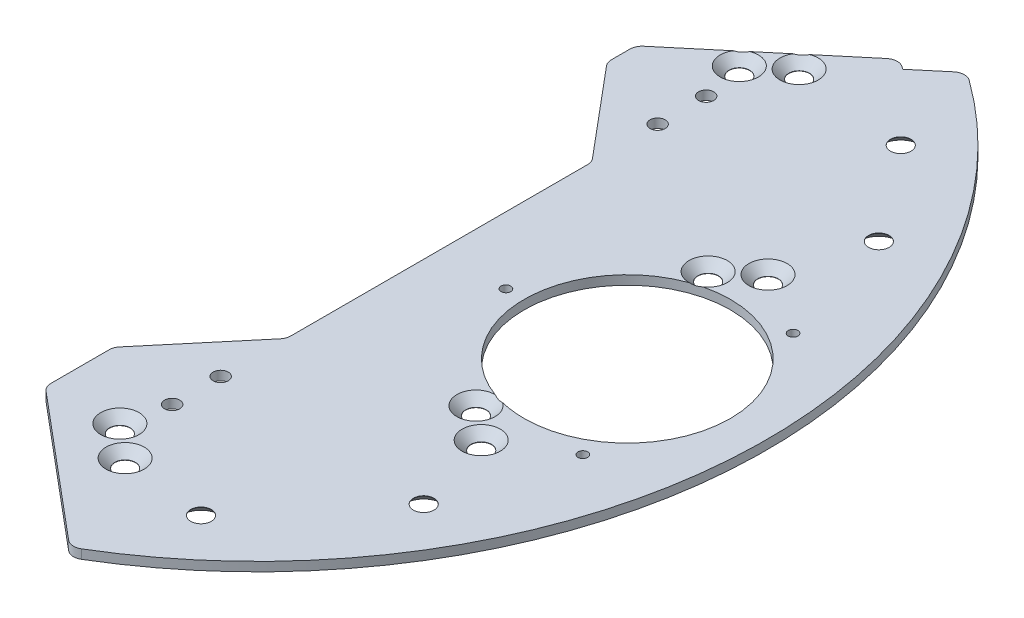
SolidWorks part; units mm, degrees
ref_plane "Plano frontal" through (0, 0, 0) normal (0, 0, 1) x (1, 0, 0)
ref_plane "Plano superior" through (0, 0, 0) normal (0, 1, 0) x (1, 0, 0)
ref_plane "Plano direito" through (0, 0, 0) normal (1, 0, 0) x (0, 0, -1)
sketch "Esboço1" plane through (0, 0, 0) normal (0, 1, 0) x (1, 0, 0)
  line L2 (0, 0) -> (17, 0) construction
  line L3 (17, -85.3229) -> (17, 85.3229)
  arc A0 (17, -85.3229) -> (17, 85.3229) centre (0, 0) ccw
  point P9 (17, 0)
  dimension "D1" = 174
  dimension "D2" = 17
extrude "Ressalto-extrusão1" add sketch "Esboço1" along normal blind 1.5 contours L3 A0
sketch "Esboço2" plane through (0, 1.5, 0) normal (0, 1, 0) x (1, 0, 0)
  line L0 (0, 0) -> (61, 0) construction
  line L1 (61, 0) -> (41, 0) construction
  line L2 (61, 0) -> (71, 17.3205) construction
  line L3 (61, 0) -> (71, -17.3205) construction
  circle A0 centre (61, 0) radius 17
  point P6 (41, 0)
  dimension "D2" = 34
  dimension "D1" = 61
  dimension "D3" = 20
  dimension "D4" = 3
extrude "Corte-extrusão1" cut sketch "Esboço2" against normal through all
hole_wizard "Furo roscado de M21" positions "3DSketch1" profile "Esboço3" tap size "M2" standard "ISO" end condition up to next
sketch3d "3DSketch1"
  point P0 (71, 1.5, 17.3205)
  point P3 (41, 1.5, 0)
  point P6 (71, 1.5, -17.3205)
sketch "Esboço3" plane through (71, 1.5, 17.3205) normal (1, 0, 0) x (0, 0, 1)
  line L0 (0, 0) -> (0, 1.5)
  line L1 (0, 1.5) -> (0.8, 1.5)
  line L2 (0.8, 1.5) -> (0.8, 0)
  line L5 (0.8, 0) -> (0, 0)
  line L11 (0, -6.35) -> (0, 107.95) construction
  dimension "Thru Tap Drill Dia." = 1.6
  dimension "Thru Tap Drill Depth" = 1.5
cosmetic thread "Rosca de furo1" parameters "D2"=2
cosmetic thread "Rosca de furo2" parameters "D2"=2
cosmetic thread "Rosca de furo3" parameters "D2"=2
sketch "Esboço4" plane through (0, 1.5, 0) normal (0, 1, 0) x (1, 0, 0)
  line L0 (0, 0) -> (66.6459, 55.9225) construction
  line L1 (0, 0) -> (61, 0) construction
  line L2 (0, 0) -> (66.6459, -55.9225) construction
  line L3 (50.8976, 74.6906) -> (82.3942, 37.1544) construction
  line L4 (82.3942, 37.1544) -> (70.8874, 27.4991) construction
  line L5 (70.8874, 27.4991) -> (55.1391, 46.2672) construction
  line L6 (55.1391, 46.2672) -> (39.3908, 65.0353) construction
  line L7 (39.3908, 65.0353) -> (50.8976, 74.6906) construction
  line L8 (48.2004, 72.4274) -> (79.697, 34.8912) construction
  line L9 (50.8976, -74.6906) -> (82.3942, -37.1544) construction
  line L10 (82.3942, -37.1544) -> (70.8874, -27.4991) construction
  line L11 (70.8874, -27.4991) -> (39.3908, -65.0353) construction
  line L12 (39.3908, -65.0353) -> (50.8976, -74.6906) construction
  line L13 (63.9487, -53.6593) -> (79.697, -34.8912) construction
  line L14 (63.9487, -53.6593) -> (48.2004, -72.4274) construction
  line L15 (17, -85.3229) -> (17, 85.3229) construction
  line L16 (30, 0) -> (30, 24.445)
  line L17 (29.5321, 25.7306) -> (17, 40.6658)
  line L18 (30, 0) -> (30, -24.445)
  line L19 (29.5321, -25.7306) -> (17, -40.6658)
  line L20 (17, 40.6658) -> (17, -40.6658)
  arc A0 (17, -85.3229) -> (17, 85.3229) centre (0, 0) ccw construction
  arc A1 (30, 24.445) -> (29.5321, 25.7306) centre (28, 24.445) ccw
  arc A2 (30, -24.445) -> (29.5321, -25.7306) centre (28, -24.445) cw
  point P17 (66.6459, -55.9225)
  point P21 (66.6459, 55.9225)
  point P24 (17, 0)
  point P26 (30, 0)
  point P36 (30, 25.173)
  point P39 (30, -25.173)
  dimension "D8" = 2
  dimension "D1" = 40
  dimension "D2" = 40
  dimension "D3" = 49
  dimension "D4" = 11.5
  dimension "D5" = 49
  dimension "D6" = 11.5
  dimension "D7" = 30
extrude "Corte-extrusão2" cut sketch "Esboço4" against normal blind 2.5
sketch "Esboço5" plane through (0, 1.5, 0) normal (0, 1, 0) x (1, 0, 0)
  line L0 (41.7531, 62.2201) -> (68.5252, 30.3144) construction
  line L2 (70.8874, 27.4991) -> (55.1391, 46.2672) construction
  line L3 (41.7531, 62.2201) -> (28.4239, 51.0356) construction
  line L4 (68.5252, 30.3144) -> (55.196, 19.1299) construction
  line L5 (0, 0) -> (66.6459, -55.9225) construction
  line L6 (70.8874, -27.4991) -> (39.3908, -65.0353) construction
  line L7 (41.7531, -62.2201) -> (68.5252, -30.3144) construction
  line L8 (41.7531, -62.2201) -> (28.4239, -51.0356) construction
  line L9 (68.5252, -30.3144) -> (55.196, -19.1299) construction
  point P0 (33.7862, 55.5351)
  point P4 (55.1391, 46.2672)
  point P10 (60.5583, 23.6294)
  point P11 (55.1391, -46.2672)
  point P12 (60.5583, -23.6294)
  point P20 (55.1391, -46.2672)
  point P22 (33.7862, -55.5351)
  dimension "D1" = 41.65
  dimension "D2" = 10.4
  dimension "D3" = 7
  dimension "D4" = 7
  dimension "D5" = 10.4
  dimension "D6" = 41.65
  dimension "D7" = 10.4
  dimension "D8" = 7
  dimension "D9" = 7
  dimension "D10" = 10.4
hole_wizard "Escareado para parafuso com cabeça escareada chata de M32" positions "3DSketch2" profile "Esboço6" countersink size "M3" standard "ISO" end condition up to next
sketch3d "3DSketch2"
  point P0 (33.7862, 1.5, -55.5351)
  point P3 (28.4239, 1.5, -51.0356)
  point P6 (60.5583, 1.5, -23.6294)
  point P9 (55.196, 1.5, -19.1299)
sketch "Esboço6" plane through (33.7862, 1.5, -55.5351) normal (1, 0, 0) x (0, 0, 1)
  line L0 (0, 0) -> (0, 1.5)
  line L1 (0, 1.5) -> (1.7, 1.5)
  line L2 (1.7, 1.5) -> (1.7, 1.45)
  line L3 (1.7, 1.45) -> (3.15, 0)
  line L5 (3.15, 0) -> (0, 0)
  line L6 (-1.7, 1.45) -> (-3.15, 0) construction
  line L11 (0, -6.35) -> (0, 107.95) construction
  dimension "Thru Hole Dia." = 3.4
  dimension "Thru Hole Depth" = 1.5
  dimension "Near C'Sink Dia." = 6.3
  dimension "Near C'Sink Angle" = 90
hole_wizard "Escareado para parafuso com cabeça escareada chata de M33" positions "3DSketch3" profile "Esboço7" countersink size "M3" standard "ISO" end condition up to next
sketch3d "3DSketch3"
  point P0 (55.196, 1.5, 19.1299)
  point P3 (60.5583, 1.5, 23.6294)
  point P6 (28.4239, 1.5, 51.0356)
  point P9 (33.7862, 1.5, 55.5351)
sketch "Esboço7" plane through (55.196, 1.5, 19.1299) normal (1, 0, 0) x (0, 0, 1)
  line L0 (0, 0) -> (0, 1.5)
  line L1 (0, 1.5) -> (1.7, 1.5)
  line L2 (1.7, 1.5) -> (1.7, 1.45)
  line L3 (1.7, 1.45) -> (3.15, 0)
  line L5 (3.15, 0) -> (0, 0)
  line L6 (-1.7, 1.45) -> (-3.15, 0) construction
  line L11 (0, -6.35) -> (0, 107.95) construction
  dimension "Thru Hole Dia." = 3.4
  dimension "Thru Hole Depth" = 1.5
  dimension "Near C'Sink Dia." = 6.3
  dimension "Near C'Sink Angle" = 90
sketch "Esboço8" plane through (0, 1.5, 0) normal (0, 1, 0) x (1, 0, 0)
  line L0 (0, 0) -> (0, 87) construction
  line L1 (27.5, 80) -> (34.1906, 80)
  line L2 (34.1906, 80) -> (34.1906, 87)
  line L3 (34.1906, 87) -> (0, 87)
  line L4 (0, 87) -> (0, 80)
  line L5 (0, 55) -> (27.5, 55)
  line L6 (27.5, 55) -> (27.5, 80)
  line L7 (0, 80) -> (27.5, 80) construction
  line L8 (0, 80) -> (0, 55)
  arc A1 (17, -85.3229) -> (17, 85.3229) centre (0, 0) ccw construction
  point P3 (0, 80)
  point P14 (27.5, 80)
  dimension "D1" = 87
  dimension "D2" = 80
  dimension "D3" = 27.5
  dimension "D4" = 25
sketch "Esboço10" plane through (0, 0, 0) normal (0, -1, 0) x (1, 0, 0)
  line L0 (0, 0) -> (78, 0) construction
  line L1 (0, 0) -> (64.9519, -37.5) construction
  line L2 (0, 0) -> (64.9519, 37.5) construction
  line L3 (0, 0) -> (48.2091, 57.4533) construction
  line L4 (0, 0) -> (53.033, -53.033) construction
  circle A0 centre (61, 0) radius 17 construction
  dimension "D1" = 30
  dimension "D2" = 45
  dimension "D3" = 50
  dimension "D4" = 30
  dimension "D5" = 75
hole_wizard "Escareado para parafuso com cabeça escareada chata de M34" positions "3DSketch4" profile "Esboço11" countersink size "M3" standard "ISO"
sketch3d "3DSketch4"
  point P0 (48.2091, 0, 57.4533)
  point P3 (64.9519, 0, 37.5)
  point P6 (64.9519, 0, -37.5)
  point P9 (53.033, 0, -53.033)
sketch "Esboço11" plane through (48.2091, 0, 57.4533) normal (1, 0, 0) x (0, 0, -1)
  line L0 (0, 0) -> (0, 8.2715)
  line L1 (0, 8.2715) -> (1.7, 7.25)
  line L2 (1.7, 7.25) -> (1.7, 1.45)
  line L3 (1.7, 1.45) -> (3.15, 0)
  line L5 (3.15, 0) -> (0, 0)
  line L6 (-1.7, 1.45) -> (-3.15, 0) construction
  line L10 (0, 8.2715) -> (-1.7, 7.25) construction
  line L11 (0, -6.35) -> (0, 107.95) construction
  dimension "Hole Dia." = 3.4
  dimension "Hole Depth" = 7.25
  dimension "Near C'Sink Dia." = 6.3
  dimension "Near C'Sink Angle" = 90
  dimension "Drill Angle" = 118
sketch "Esboço15" plane through (0, 0, 0) normal (0, -1, 0) x (1, 0, 0)
  line L0 (0, 0) -> (42.4264, 42.4264) construction
  line L1 (0, 0) -> (61, 0)
  line L2 (58.3363, 26.5165) -> (26.5165, 58.3363)
  line L3 (58.3363, 26.5165) -> (40.6586, 8.8388)
  line L4 (40.6586, 8.8388) -> (8.8388, 40.6586)
  line L5 (8.8388, 40.6586) -> (26.5165, 58.3363)
  point P2 (26.5165, 44.1942)
  point P6 (42.4264, 42.4264)
  point P9 (14.4957, 42.0729)
  point P10 (42.0729, 14.4957)
  point P14 (52.6795, 25.1023)
  dimension "D1" = 45
  dimension "D2" = 60
  dimension "D3" = 45
  dimension "D4" = 25
  dimension "D5" = 3
  dimension "D6" = 3
  dimension "D7" = 10
  dimension "D8" = 10
  dimension "D9" = 5
  dimension "D10" = 20
  dimension "D11" = 3
  dimension "D12" = 5
sketch "Esboço17" plane through (0, 0, 0) normal (0, -1, 0) x (1, 0, 0)
  line L0 (28.4239, -51.0356) -> (33.7862, -55.5351) construction
  line L1 (28.4239, -51.0356) -> (26.4956, -53.3337) construction
  line L2 (26.4956, -53.3337) -> (17, -45.366)
  line L4 (17, -40.6658) -> (17, -85.3229) construction
  line L5 (17, -45.366) -> (17, -85.3229)
  line L6 (26.4956, -53.3337) -> (48.7837, -72.0357)
  line L7 (48.7837, -72.0357) -> (48.7837, -85.3229)
  line L8 (48.7837, -85.3229) -> (17, -85.3229)
  arc A0 (17, -85.3229) -> (17, 85.3229) centre (0, 0) ccw construction
  dimension "D1" = 3
extrude "Corte-extrusão3" cut sketch "Esboço17" against normal through all
sketch "Esboço18" plane through (0, 1.5, 0) normal (0, 1, 0) x (1, 0, 0)
  line L0 (33.7862, -55.5351) -> (28.4239, -51.0356) construction
  line L1 (28.4239, -51.0356) -> (23.2816, -57.164) construction
  line L2 (23.2816, -57.164) -> (17, -51.8931)
  line L3 (17, -85.3229) -> (17, -40.6658) construction
  line L4 (17, -51.8931) -> (17, -85.3229)
  line L5 (17, -85.3229) -> (56.8402, -85.3229)
  line L6 (56.8402, -85.3229) -> (23.2816, -57.164)
  dimension "D1" = 8
extrude "Corte-extrusão4" cut sketch "Esboço18" against normal through all contours L5 L6 L2 L4
sketch "Esboço19" plane through (0, 1.5, 0) normal (0, 1, 0) x (1, 0, 0)
  line L0 (48.7837, 72.0357) -> (32.5936, 58.4506) construction
  line L1 (44.3532, -74.8451) -> (17, -51.8931) construction
  line L2 (48.7837, 72.0357) -> (46.3908, 70.0278)
  line L3 (41.9121, -72.7968) -> (44.3532, -74.8451)
  arc A0 (44.3532, -74.8451) -> (48.7837, 72.0357) centre (0, 0) ccw
  arc A1 (44.3532, -74.8451) -> (48.7837, 72.0357) centre (0, 0) ccw construction
  arc A2 (46.3908, 70.0278) -> (41.9121, -72.7968) centre (0, 0) cw
  dimension "D1" = 84
extrude "Corte-extrusão5" cut sketch "Esboço19" against normal through all
sketch "Esboço20" plane through (0, 1.5, 0) normal (0, 1, 0) x (1, 0, 0)
  line L0 (41.0285, 65.5283) -> (42.314, 63.9962)
  line L1 (46.3908, 70.0278) -> (32.5936, 58.4506) construction
  line L2 (42.314, 63.9962) -> (48.109, 68.8587)
  line L3 (41.0285, 65.5283) -> (46.8234, 70.3908)
  line L4 (48.109, 68.8587) -> (46.8234, 70.3908)
  arc A0 (41.9121, -72.7968) -> (46.3908, 70.0278) centre (0, 0) ccw construction
  dimension "D1" = 2
  dimension "D2" = 7
extrude "Corte-extrusão6" cut sketch "Esboço20" against normal through all
fillet "Filete2" radius 2 7 edges at (17, 0.75, 40.6658) (17, 0.75, 51.8931) (41.9121, 0.75, 72.7968) (48.109, 0.75, -68.8587) (41.0285, 0.75, -65.5283) (17, 0.75, -40.6658) (17, 0.75, -45.366)
sketch "Esboço21" plane through (0, 1.5, 0) normal (0, 1, 0) x (1, 0, 0)
  line L0 (0, 0) -> (84, 0) construction
  line L1 (0, 0) -> (0, 40) construction
  line L2 (0, 40) -> (30, 40) construction
  line L3 (30, 44) -> (30, 36)
  line L4 (0, 0) -> (0, -40) construction
  line L5 (0, -40) -> (30, -40) construction
  line L6 (30, -44) -> (30, -36)
  arc A0 (43.1439, -72.0736) -> (49.3847, 67.9496) centre (0, 0) ccw construction
  point P12 (30, 40)
  point P18 (30, -40)
  dimension "D1" = 40
  dimension "D2" = 30
  dimension "D3" = 8
  dimension "D4" = 40
  dimension "D5" = 30
  dimension "D6" = 8
hole_wizard "Broca de rosquear para tarraxa de M31" positions "3DSketch5" profile "Esboço22" hole size "M3" standard "ISO" end condition through all
sketch3d "3DSketch5"
  point P0 (30, 1.5, 44)
  point P3 (30, 1.5, 36)
  point P6 (30, 1.5, -44)
  point P9 (30, 1.5, -36)
sketch "Esboço22" plane through (30, 1.5, 44) normal (1, 0, 0) x (0, 0, 1)
  line L0 (0, 0) -> (0, 1.5)
  line L1 (0, 1.5) -> (1.25, 1.5)
  line L2 (1.25, 1.5) -> (1.25, 0)
  line L5 (1.25, 0) -> (0, 0)
  line L11 (0, -6.35) -> (0, 107.95) construction
  dimension "Thru Hole Dia." = 2.5
  dimension "Thru Hole Depth" = 1.5
